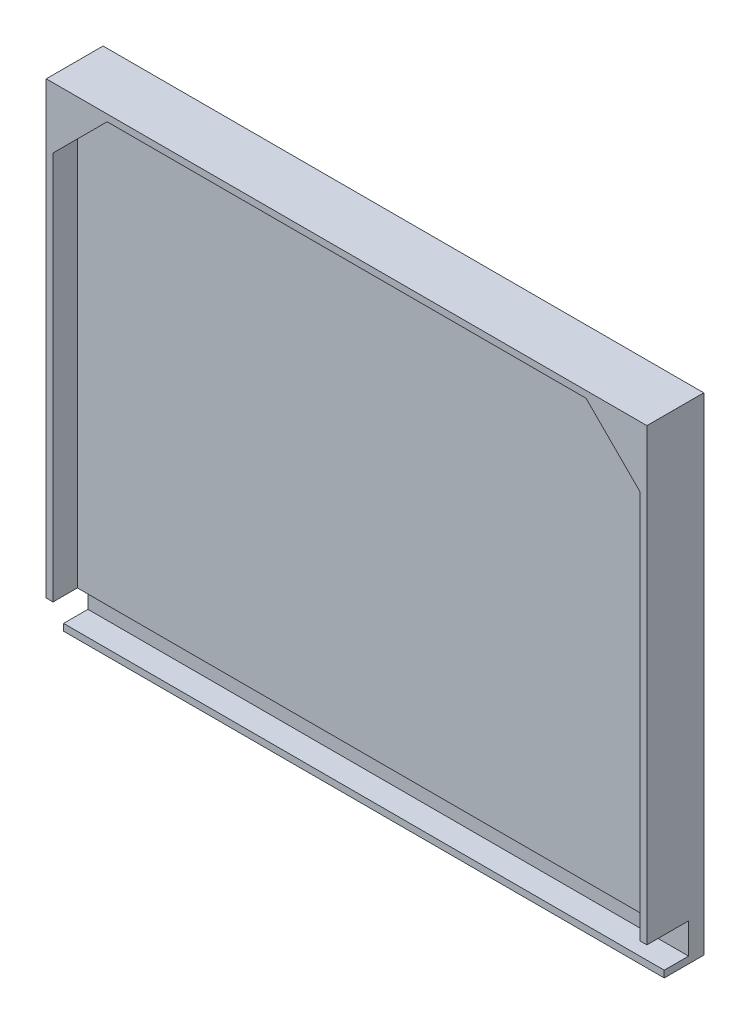
SolidWorks part; units mm, degrees
ref_plane "Front Plane" through (0, 0, 0) normal (0, 0, 1) x (1, 0, 0)
ref_plane "Top Plane" through (0, 0, 0) normal (0, 1, 0) x (1, 0, 0)
ref_plane "Right Plane" through (0, 0, 0) normal (1, 0, 0) x (0, 0, -1)
sketch "Sketch1" plane through (0, 0, 0) normal (0, 0, 1) x (1, 0, 0)
  line L1 (-68.3632, 130.6396) -> (213.5768, 130.6396)
  line L2 (-68.3632, 130.6396) -> (-68.3632, -97.9604)
  line L3 (-68.3632, -97.9604) -> (213.5768, -97.9604)
  line L4 (213.5768, 130.6396) -> (213.5768, -97.9604)
  dimension "D1" = 281.94
  dimension "D2" = 228.6
extrude "Boss-Extrude2" add sketch "Sketch1" along normal blind 25.4
sketch "Sketch3" plane through (0, 0, 25.4) normal (0, 0, 1) x (1, 0, 0)
  line L0 (-68.3632, -97.9604) -> (-68.3632, -80.4344)
  line L1 (-68.3632, 130.6396) -> (-68.3632, -97.9604) construction
  line L2 (-68.3632, -80.4344) -> (213.5768, -80.4344)
  line L3 (213.5768, -97.9604) -> (213.5768, 130.6396) construction
  line L4 (213.5768, -80.4344) -> (213.5768, -97.9604)
  line L5 (213.5768, -97.9604) -> (-68.3632, -97.9604)
  dimension "D1" = 17.526
extrude "Cut-Extrude1" cut sketch "Sketch3" against normal blind 8.128
sketch "Sketch4" plane through (-68.3632, 0, 0) normal (-1, 0, 0) x (0, 0, 1)
  line L0 (25.4, 130.6396) -> (36.83, 130.6396)
  line L1 (36.83, 130.6396) -> (36.83, -80.4344)
  line L2 (36.83, -80.4344) -> (25.4, -80.4344)
  line L3 (25.4, -80.4344) -> (25.4, 130.6396)
  dimension "D1" = 11.43
extrude "Boss-Extrude4" add sketch "Sketch4" against normal blind 3.175 separate body
sketch "Sketch5" plane through (0, 130.6396, 0) normal (0, 1, 0) x (1, 0, 0)
  line L15 (-65.1882, -36.83) -> (-65.1882, -25.4)
  line L16 (-65.1882, -25.4) -> (213.5768, -25.4)
  line L17 (213.5768, -25.4) -> (213.5768, -36.83)
  line L18 (213.5768, -36.83) -> (-65.1882, -36.83)
sketch "Sketch8" plane through (0, -97.9604, 0) normal (0, -1, 0) x (1, 0, 0)
  line L0 (-68.3632, 17.272) -> (-68.3632, 28.702)
  line L1 (-68.3632, 28.702) -> (213.5768, 28.702)
  line L2 (213.5768, 28.702) -> (213.5768, 17.272)
  line L3 (213.5768, 17.272) -> (-68.3632, 17.272)
  dimension "D1" = 11.43
extrude "Boss-Extrude9" add sketch "Sketch5" against normal blind 3.175
sketch "Sketch9" plane through (213.5768, 0, 0) normal (1, 0, 0) x (0, 0, -1)
  line L0 (-25.4, -80.4344) -> (-36.83, -80.4344)
  line L1 (-36.83, -80.4344) -> (-36.83, 127.4646)
  line L2 (-36.83, 127.4646) -> (-25.4, 127.4646)
  line L3 (-25.4, 127.4646) -> (-25.4, -80.4344)
  dimension "D1" = 11.43
extrude "Boss-Extrude10" add sketch "Sketch9" against normal blind 3.175
extrude "Boss-Extrude11" add sketch "Sketch8" against normal blind 3.175 separate body
combine bodies "Combine1" operation type add bodies to combine 115 114
sketch "Sketch10" plane through (0, 0, 17.272) normal (0, 0, 1) x (1, 0, 0)
  line L0 (213.5768, -80.4344) -> (213.5768, -94.7854)
  line L1 (213.5768, -94.7854) -> (-68.3632, -94.7854)
  line L2 (-68.3632, -94.7854) -> (-68.3632, -80.4344)
  line L3 (-68.3632, -80.4344) -> (213.5768, -80.4344)
extrude "Cut-Extrude2" cut sketch "Sketch10" against normal blind 10.16
sketch "Sketch11" plane through (0, 0, 25.4) normal (0, 0, 1) x (1, 0, 0)
  line L0 (210.4018, 127.4646) -> (210.4018, -80.4344)
  line L1 (210.4018, -80.4344) -> (-65.1882, -80.4344)
  line L2 (-65.1882, -80.4344) -> (-65.1882, 127.4646)
  line L3 (-65.1882, 127.4646) -> (210.4018, 127.4646)
extrude "Cut-Extrude3" cut sketch "Sketch11" against normal blind 10.16
sketch "Sketch12" plane through (0, 0, 36.83) normal (0, 0, 1) x (1, 0, 0)
  line L0 (-68.3632, -80.4344) -> (-65.1882, -80.4344)
  line L1 (-65.1882, -80.4344) -> (-65.1882, 127.4646)
  line L2 (-65.1882, 127.4646) -> (210.4018, 127.4646)
  line L3 (210.4018, 127.4646) -> (210.4018, -80.4344)
  line L4 (210.4018, -80.4344) -> (213.5768, -80.4344)
  line L5 (213.5768, -80.4344) -> (213.5768, 130.6396)
  line L6 (213.5768, 130.6396) -> (-68.3632, 130.6396)
  line L7 (-68.3632, 130.6396) -> (-68.3632, -80.4344)
extrude "Cut-Extrude4" cut sketch "Sketch12" against normal blind 10.16
sketch "Sketch13" plane through (0, 0, 28.702) normal (0, 0, 1) x (1, 0, 0)
  line L0 (-68.3632, -94.7854) -> (-68.3632, -97.9604)
  line L1 (-68.3632, -97.9604) -> (213.5768, -97.9604)
  line L2 (213.5768, -97.9604) -> (213.5768, -94.7854)
  line L3 (213.5768, -94.7854) -> (-68.3632, -94.7854)
extrude "Cut-Extrude5" cut sketch "Sketch13" against normal blind 10.16
shell "Shell4" thickness 2.54
sketch "Sketch14" plane through (0, 0, 26.67) normal (0, 0, 1) x (1, 0, 0)
  line L1 (-65.1882, 102.0646) -> (-39.7882, 127.4646)
  line L2 (-65.1882, -80.4344) -> (-65.1882, 127.4646) construction
  line L3 (-65.1882, 127.4646) -> (210.4018, 127.4646) construction
  line L4 (-39.7882, 127.4646) -> (-65.1882, 127.4646)
  line L5 (-65.1882, 127.4646) -> (-65.1882, 102.0646)
  line L6 (185.0018, 127.4646) -> (210.4018, 102.0646)
  line L7 (210.4018, 127.4646) -> (210.4018, -80.4344) construction
  line L8 (210.4018, 102.0646) -> (210.4018, 127.4646)
  line L9 (210.4018, 127.4646) -> (185.0018, 127.4646)
  dimension "D1" = 25.4
  dimension "D2" = 25.4
  dimension "D3" = 25.4
  dimension "D4" = 25.4
extrude "Boss-Extrude12" add sketch "Sketch14" against normal blind 3.175
